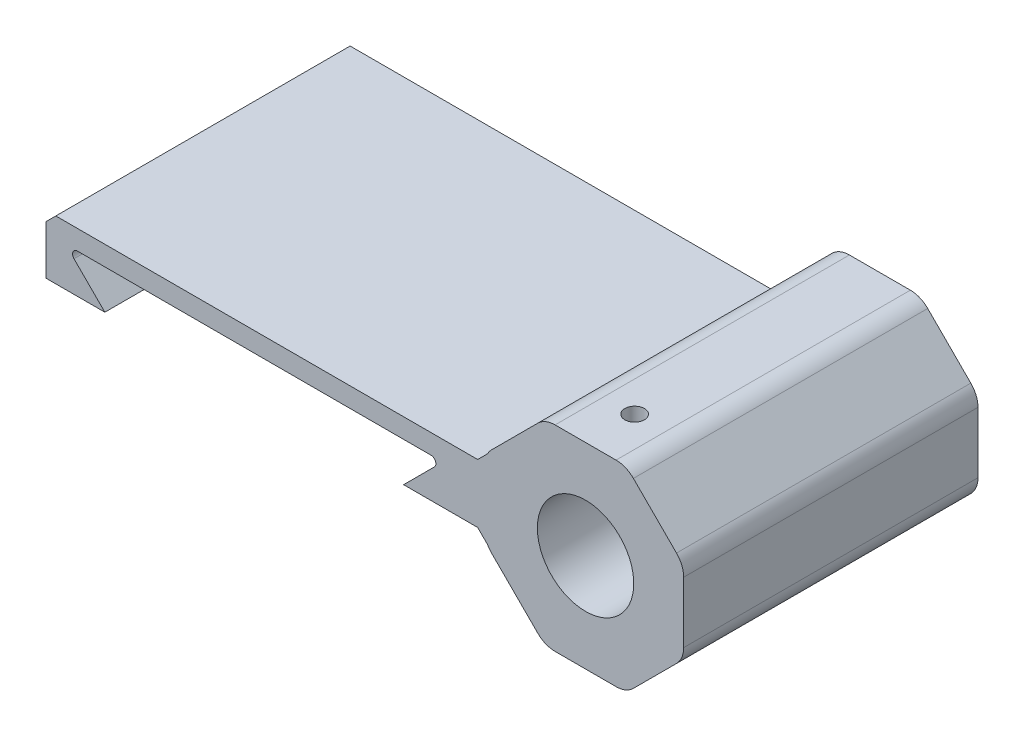
SolidWorks part; units mm, degrees
ref_plane "Спереди" through (0, 0, 0) normal (0, 0, 1) x (1, 0, 0)
ref_plane "Сверху" through (0, 0, 0) normal (0, 1, 0) x (1, 0, 0)
ref_plane "Справа" through (0, 0, 0) normal (1, 0, 0) x (0, 0, -1)
other "Configuration Table"
sketch "Эскиз1" plane through (0, 0, 0) normal (0, 0, 1) x (1, 0, 0)
  line L1 (-45, -6) -> (45, -6)
  line L2 (-45, -6) -> (-45, 6)
  line L3 (-45, 6) -> (45, 6)
  line L4 (45, -6) -> (45, 6)
  line L5 (-45, -6) -> (45, 6) construction
  line L6 (-45, 6) -> (45, -6) construction
  point P0 (0, 0)
  dimension "D1" = 12
  dimension "D2" = 90
extrude "Бобышка-Вытянуть1" add sketch "Эскиз1" along normal blind 60
sketch "Эскиз2" plane through (0, 0, 60) normal (0, 0, 1) x (1, 0, 0)
  line L0 (-41, 2) -> (-33, -6)
  line L1 (-45, -6) -> (45, -6) construction
  line L2 (-45, 6) -> (-45, -6) construction
  line L3 (-33, -6) -> (27.9, -6)
  line L4 (27.9, -6) -> (35.9, 2)
  line L5 (35.9, 2) -> (-41, 2)
  dimension "D1" = 8
  dimension "D2" = 45
  dimension "D3" = 12
  dimension "D4" = 60.9
extrude "Вырез-Вытянуть1" cut sketch "Эскиз2" against normal up to surface (60 mm away) up to face at (0, 0, 0)
sketch "Эскиз3" plane through (0, 0, 0) normal (0, 0, -1) x (-1, 0, 0)
  line L0 (-45, 0) -> (-87.7248, 0) construction
  line L1 (-45, -6) -> (-45, 6) construction
  line L2 (-73.2843, -20) -> (-56.7157, -20)
  line L3 (-45, -8.2843) -> (-45, 8.2843)
  line L4 (-45, 8.2843) -> (-56.7157, 20)
  line L5 (-56.7157, 20) -> (-73.2843, 20)
  line L6 (-73.2843, 20) -> (-85, 8.2843)
  line L7 (-85, 8.2843) -> (-85, -8.2843)
  line L8 (-85, -8.2843) -> (-73.2843, -20)
  line L9 (-56.7157, -20) -> (-45, -8.2843)
  circle A0 centre (-65, 0) radius 20 construction
  circle A1 centre (-65, 0) radius 9.825
  dimension "D1" = 40
  dimension "D2" = 19.65
extrude "Бобышка-Вытянуть2" add sketch "Эскиз3" against normal up to surface (60 mm away) up to face at (-1.275, -1, 60)
chamfer "Фаска1" distance 2 angle 45 1 edges at (-45, 6, 30)
fillet "Скругление1" radius 1 2 edges at (35.9, 2, 30) (-41, 2, 30)
chamfer "Фаска3" distance 2 angle 45 2 edges at (45, -6, 30) (45, 6, 30)
fillet "Скругление2" radius 5 8 edges at (45, -8.2843, 30) (56.7157, -20, 30) (73.2843, -20, 30) (85, -8.2843, 30) (85, 8.2843, 30) (73.2843, 20, 30) (56.7157, 20, 30) (45, 8.2843, 30)
sketch "Эскиз4" plane through (0, 20, 0) normal (0, 1, 0) x (1, 0, 0)
  line L0 (65, 0) -> (65, -60) construction
  line L1 (58.7868, 0) -> (71.2132, 0) construction
  line L2 (71.2132, -60) -> (58.7868, -60) construction
  circle A0 centre (65, -50) radius 2
  dimension "D1" = 4
  dimension "D2" = 10
extrude "Вырез-Вытянуть2" cut sketch "Эскиз4" against normal up to surface (10.175 mm away) up to face at (55.175, 0, 60)
